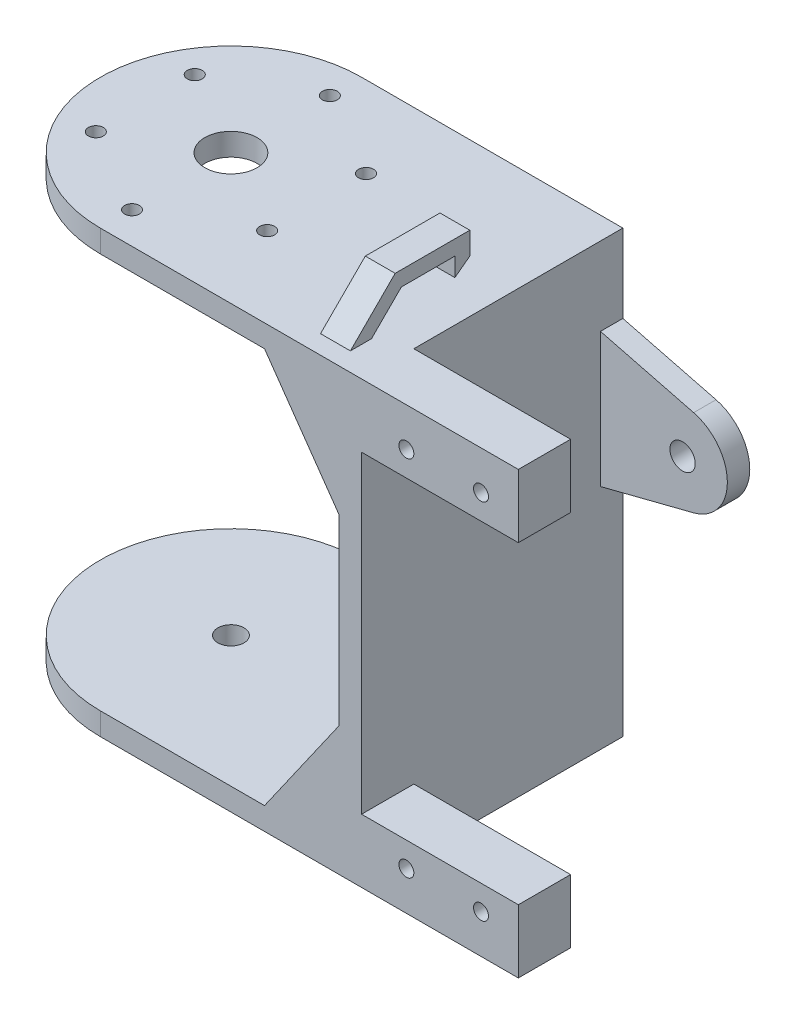
SolidWorks part; units mm, degrees
ref_plane "Plano frontal" through (0, 0, 0) normal (0, 0, 1) x (1, 0, 0)
ref_plane "Plano superior" through (0, 0, 0) normal (0, 1, 0) x (1, 0, 0)
ref_plane "Plano direito" through (0, 0, 0) normal (1, 0, 0) x (0, 0, -1)
sketch "Esboço1" plane through (0, 0, 0) normal (0, 0, 1) x (1, 0, 0)
  line L1 (0, -29.5) -> (-53, -29.5)
  line L2 (-53, -29.5) -> (-53, -26.5)
  line L3 (-53, -26.5) -> (-3, -26.5)
  line L4 (-3, -26.5) -> (-3, 26.5)
  line L5 (-3, 26.5) -> (-53, 26.5)
  line L6 (-53, 26.5) -> (-53, 29.5)
  line L7 (-53, 29.5) -> (1, 29.5)
  line L8 (1, 29.5) -> (21, 29.5)
  line L9 (21, 29.5) -> (21, 21)
  line L10 (21, 21) -> (0, 21)
  line L11 (0, -29.5) -> (21, -29.5)
  line L12 (21, -29.5) -> (21, -21)
  line L13 (21, -21) -> (0, -21)
  line L14 (0, 21) -> (0, -21)
  line L16 (6, 24.315) -> (16, 24.315) construction
  line L17 (0, 0) -> (31.9596, 0) construction
  circle A0 centre (16, 24.315) radius 1
  circle A1 centre (6, 24.315) radius 1
  circle A2 centre (16, -24.315) radius 1
  circle A3 centre (6, -24.315) radius 1
  point P4 (0, 0)
  point P19 (0, 0)
  point P20 (-3, 0)
  point P24 (11, 24.315)
  point P25 (11, 29.5)
  dimension "D9" = 2
  dimension "D1" = 42
  dimension "D2" = 3
  dimension "D3" = 21
  dimension "D4" = 20
  dimension "D5" = 3
  dimension "D6" = 53
  dimension "D7" = 50
  dimension "D8" = 10
  dimension "D10" = 48.63
extrude "Ressalto-extrusão1" add sketch "Esboço1" along normal mid plane 35
sketch "Esboço2" plane through (0, 29.5, 0) normal (0, 1, 0) x (1, 0, 0)
  line L0 (-35, 17.5) -> (-53, 17.5)
  line L1 (-53, 17.5) -> (-53, -17.5)
  line L2 (0, 0) -> (-11.2728, 0) construction
  line L3 (-53, -17.5) -> (-35, -17.5)
  circle A0 centre (-35, 0) radius 3.5
  circle A1 centre (-35, 13.25) radius 1
  circle A2 centre (-23.5252, 6.625) radius 1
  circle A3 centre (-23.5252, -6.625) radius 1
  circle A4 centre (-35, -13.25) radius 1
  circle A5 centre (-46.4748, -6.625) radius 1
  circle A6 centre (-46.4748, 6.625) radius 1
  arc A7 (-35, 17.5) -> (-35, -17.5) centre (-35, 0) ccw
  point P19 (-35, 0)
  line M3 (21, 17.5) -> (-53, 17.5)
  line M4 (-53, 17.5) -> (-53, -17.5)
  line M5 (-53, -17.5) -> (21, -17.5)
  dimension "D1" = 7
  dimension "D3" = 2
  dimension "D2" = 13.25
  dimension "D4" = 35
  dimension "D5" = 6
extrude "Corte-extrusão1" cut sketch "Esboço2" against normal blind 15
sketch "Esboço4" plane through (0, -21, 0) normal (0, 1, 0) x (1, 0, 0)
  line L0 (21, -17.5) -> (21, 17.5) construction
  line L1 (21, -10.5) -> (0, -10.5)
  line L2 (21, -10.5) -> (21, 17.5)
  line L3 (21, 17.5) -> (0, 17.5)
  line L4 (0, -10.5) -> (0, 17.5)
  line L5 (21, -17.5) -> (0, -17.5) construction
  dimension "D1" = 7
extrude "Corte-extrusão2" cut sketch "Esboço4" against normal through all both and the other way through all
sketch "Esboço5" plane through (0, 0, -17.5) normal (0, 0, -1) x (-1, 0, 0)
  line L0 (-6, 24.315) -> (-16, 24.315) construction
  line L1 (-12.4839, 15.8286) -> (0, 19.015)
  line L2 (0, -21) -> (0, 21) construction
  line L3 (-12.4839, 4.2014) -> (0, 1.015)
  line L4 (0, 19.015) -> (0, 1.015)
  arc A0 (-12.4839, 15.8286) -> (-12.4839, 4.2014) centre (-11, 10.015) ccw
  circle A1 centre (-11, 10.015) radius 1.7
  point P8 (-11, 24.315)
  dimension "D1" = 3.4
  dimension "D3" = 6
  dimension "D2" = 14.3
  dimension "D4" = 18
extrude "Ressalto-extrusão2" add sketch "Esboço5" against normal blind 3
chamfer "Chanfro1" distance 10 angle 55 2 edges at (-3, -26.5, 0) (-3, 26.5, 0) first distance on face at (-28, -26.5, 0) first distance on face at (-47.4748, 26.5, -6.625)
sketch "Esboço7" plane through (0, -26.5, 0) normal (0, 1, 0) x (1, 0, 0)
  circle A0 centre (-35, 0) radius 1.75
  dimension "D1" = 3.5
extrude "Corte-extrusão3" cut sketch "Esboço7" against normal blind 10
extrude "Corte-extrusão4" cut sketch "Esboço2<2>" against normal through all contours A7 M3 M4 M5 region at (-52.8936, 29.5, 0)
sketch "Esboço2<2>" plane through (0, 29.5, 0) normal (0, 1, 0) x (1, 0, 0) same geometry as "Esboço2"
sketch "Esboço8" plane through (0, 0, 0) normal (1, 0, 0) x (0, 0, -1)
  line L0 (-15, 29.5) -> (-9, 35.5)
  line L1 (-17.5, 29.5) -> (-10.5, 29.5) construction
  line L2 (-9, 35.5) -> (1, 35.5)
  line L3 (1, 35.5) -> (1, 32.5)
  line L4 (1, 32.5) -> (-1, 31)
  line L5 (-1, 31) -> (-1, 33.5)
  line L6 (-1, 33.5) -> (-8.1716, 33.5)
  line L7 (-8.1716, 33.5) -> (-12.1716, 29.5)
  line L8 (-12.1716, 29.5) -> (-15, 29.5)
  line L9 (-4.5858, 35.5) -> (-4.5858, 33.5) construction
  line L13 (-8.1716, 33.5) -> (-9.5858, 34.9142) construction
  point P14 (-4.5858, 33.5)
  dimension "D1" = 4
  dimension "D2" = 2
  dimension "D3" = 3
  dimension "D4" = 1.5
  dimension "D5" = 2
  dimension "D6" = 10
  dimension "D7" = 45
  dimension "D8" = 2.5
extrude "Ressalto-extrusão3" add sketch "Esboço8" against normal blind 4 from offset 4 offset against normal yes
sketch "Esboço9" plane through (0, -26.5, 0) normal (0, 1, 0) x (1, 0, 0)
  line L0 (-13, 17.5) -> (-35, 17.5) construction
  line L1 (-13, -17.5) -> (-35, -17.5) construction
  line L2 (-18.5759, 17.5) -> (-18.5759, -17.5)
  arc A0 (-18.5759, 17.5) -> (-18.5759, -17.5) centre (-35, 0) cw
  point P3 (-18.5759, -17.1083)
  dimension "D1" = 24
extrude "Corte-extrusão5" cut sketch "Esboço9" along normal up to surface (53 mm away) up to face at (-47.4748, 26.5, -6.625)
